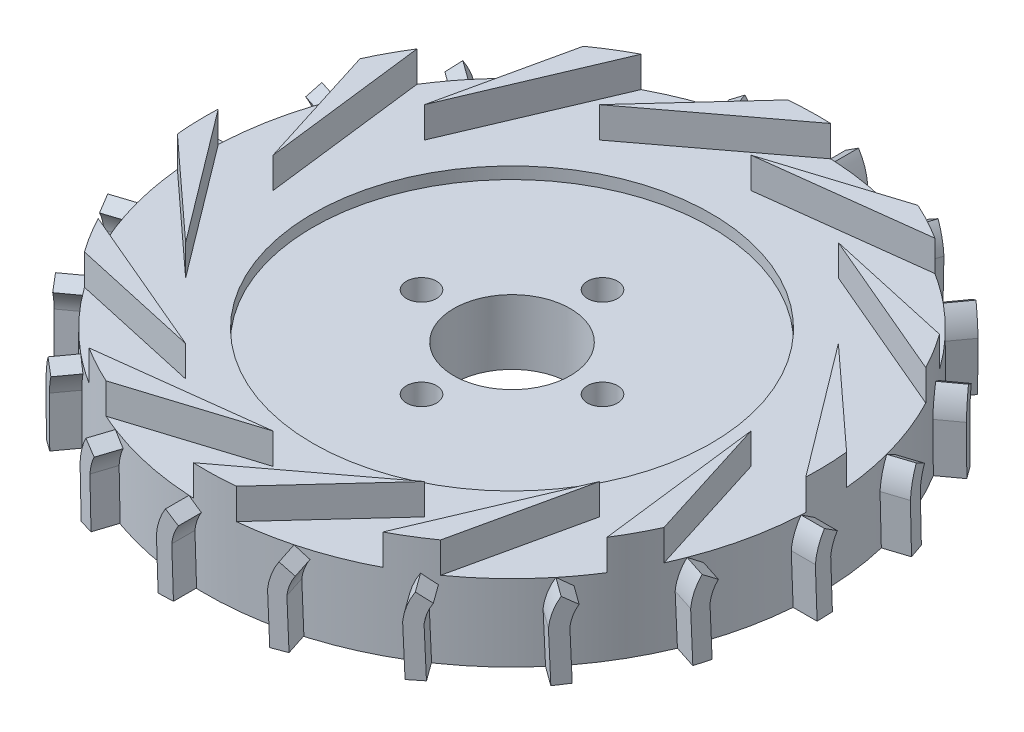
SolidWorks part; units mm, degrees
ref_plane "Front Plane" through (0, 0, 0) normal (0, 0, 1) x (1, 0, 0)
ref_plane "Top Plane" through (0, 0, 0) normal (0, 1, 0) x (1, 0, 0)
ref_plane "Right Plane" through (0, 0, 0) normal (1, 0, 0) x (0, 0, -1)
sketch "Sketch1" plane through (0, 0, 0) normal (1, 0, 0) x (0, 0, -1)
  line L0 (0, 26.2631) -> (0, -3.5886) construction
  line L1 (0, -3.5886) -> (-50.8, -3.5886)
  line L2 (-50.8, -3.5886) -> (-50.8, 9.1114)
  line L3 (-33.0001, 9.1114) -> (-50.8, 9.1114)
  line L4 (-33.0001, 9.1114) -> (-33.0001, 7.1515)
  line L5 (-33.0001, 7.1515) -> (0, 7.1515)
  line L6 (0, 7.1515) -> (0, -3.5886)
  dimension "D1" = 33.0001
  dimension "D2" = 50.8
  dimension "D3" = 1.96
  dimension "D4" = 12.7
revolve "Revolve1" add sketch "Sketch1" angle 360 about L0
sketch "Sketch2" plane through (0, 9.1114, 0) normal (0, 1, 0) x (1, 0, 0)
  line L8 (0, 39.6001) -> (19.9397, 39.6001) construction
  line L9 (0, 39.6001) -> (21.0453, 46.2356)
  line L10 (0, 39.6001) -> (27.1669, 42.9255)
  circle A0 centre (0, 0) radius 50.8 construction
  arc A1 (21.0453, 46.2356) -> (27.1669, 42.9255) centre (0, 0) cw
  circle A5 centre (0, 0) radius 33.0001 construction
  circle A7 centre (0, 0) radius 39.6001 construction
  point P9 (-2.4416, -40.4611)
  dimension "D1" = 66.0001
  dimension "D2" = 79.2001
  dimension "D3" = 17.5
extrude "Boss-Extrude1" add sketch "Sketch2" along normal blind 5.08
pattern_circular "CirPattern1" count 12 over 360 about axis through (0, 9.1114, 0) along (0, 1, 0) of "Boss-Extrude1"
ref_plane "Plane1" through (0, 0, 49.53) normal (0, 0, 1) x (1, 0, 0)
sketch "Sketch3" plane through (0, 0, 49.53) normal (0, 0, 1) x (1, 0, 0)
  line L0 (0, 0) -> (0, 9.7621) construction
  line L1 (0, -9.779) -> (0, 9.779) construction
  line L5 (-21.0453, 9.1114) -> (0, 9.1114) construction
  line L6 (-50.8, -3.5886) -> (50.8, -3.5886) construction
  line L7 (-4.3287, 4.6923) -> (-4.0403, -3.5886)
  line L10 (-1.7845, 4.6163) -> (-1.5018, -3.5001)
  line L11 (-0.685, 7.735) -> (-2.8198, 9.1114)
  line L12 (-4.0403, -3.5886) -> (-1.5018, -3.5001)
  arc A4 (-2.8198, 9.1114) -> (-4.3287, 4.6923) centre (5.3144, 3.8668) ccw
  arc A5 (-0.685, 7.735) -> (-1.7845, 4.6163) centre (5.3144, 3.8668) ccw
  dimension "D1" = 2.54
extrude "Boss-Extrude2" add sketch "Sketch3" along normal blind 5.08 and the other way blind 0.254
pattern_circular "CirPattern16" count 20 over 360 about axis through (0, -3.5886, 0) along (0, 1, 0) of "Boss-Extrude2"
sketch "Sketch4" plane through (0, 7.1515, 0) normal (0, 1, 0) x (1, 0, 0)
  circle A0 centre (0, 0) radius 9.652
  dimension "D1" = 19.304
extrude "Cut-Extrude1" cut sketch "Sketch4" against normal up to next
sketch "Sketch5" plane through (0, -3.5886, 0) normal (0, -1, 0) x (-1, 0, 0)
  circle A0 centre (0, 0) radius 38.1
  dimension "D1" = 76.2
extrude "Cut-Extrude2" cut sketch "Sketch5" against normal blind 7.62
sketch "Sketch6" plane through (0, 4.0314, 0) normal (0, -1, 0) x (1, 0, 0)
  circle A0 centre (0, 0) radius 19.05
  circle A1 centre (0, 0) radius 9.652 construction
  circle A2 centre (0, 0) radius 9.652
  dimension "D1" = 38.1
extrude "Boss-Extrude3" add sketch "Sketch6" along normal up to surface (7.62 mm away) up to face at (0, -3.5886, -38.1)
sketch "Sketch9" plane through (0, 7.1515, 0) normal (0, 1, 0) x (1, 0, 0)
  circle A0 centre (0, 15) radius 2.5
  dimension "D1" = 5
  dimension "D2" = 15
extrude "Cut-Extrude3" cut sketch "Sketch9" against normal up to next
pattern_circular "CirPattern17" count 4 over 360 about axis through (0, 7.1515, 0) along (0, 1, 0) of "Cut-Extrude3"
